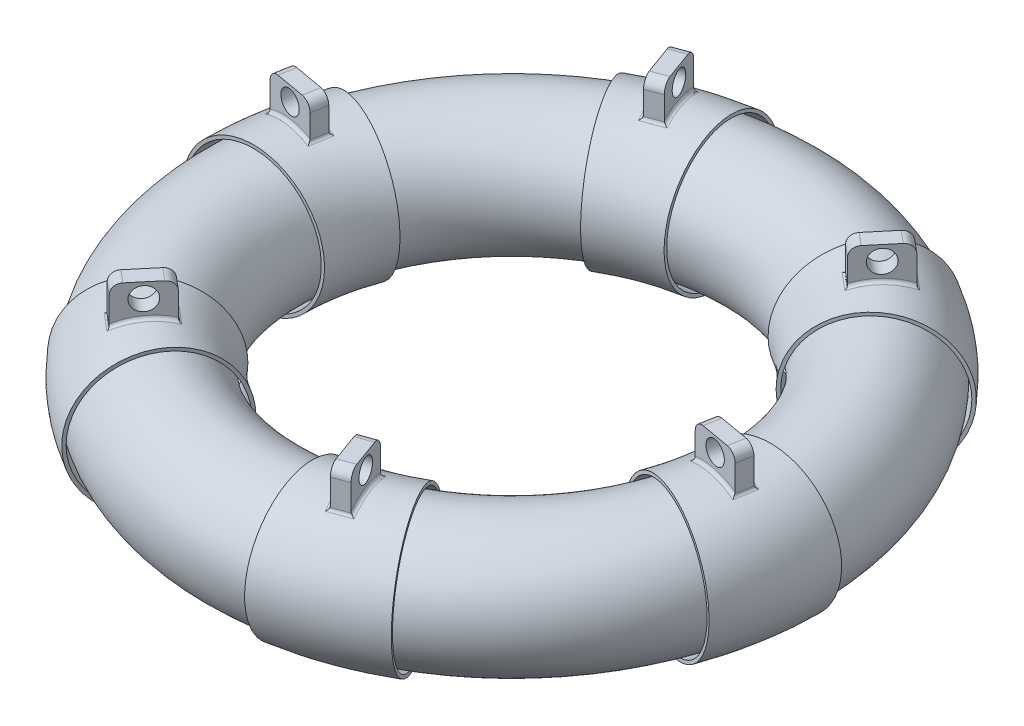
SolidWorks part; units mm, degrees
ref_plane "Front Plane" through (0, 0, 0) normal (0, 0, 1) x (1, 0, 0)
ref_plane "Top Plane" through (0, 0, 0) normal (0, 1, 0) x (1, 0, 0)
ref_plane "Right Plane" through (0, 0, 0) normal (1, 0, 0) x (0, 0, -1)
sketch "Sketch1" plane through (0, 0, 0) normal (0, 0, 1) x (1, 0, 0)
  line L0 (0, 0) -> (-100, 0) construction
  line L1 (0, 14.2155) -> (0, -15.5415) construction
  circle A0 centre (-80, 0) radius 20
  dimension "D2" = 40
  dimension "D1" = 100
revolve "Revolve1" add sketch "Sketch1" angle 360 about L1
sketch "Sketch2" plane through (0, 0, 0) normal (0, 0, 1) x (1, 0, 0)
  line L0 (0, 0) -> (0, 19.2706) construction
  line L1 (110, 0) -> (-110, 0) construction
  circle A0 centre (-80, 0) radius 21
revolve "Revolve-Thin1" add sketch "Sketch2" angle 20 about L0
sketch "Sketch3" plane through (0, 0, 0) normal (0, 1, 0) x (1, 0, 0)
  line L0 (0, 0) -> (-100.4504, 17.7121) construction
  line L1 (-100.4504, 17.7121) -> (-79.8488, 14.0795) construction
  line L3 (-86.9146, 17.864) -> (-71.9146, 15.2191)
  line L4 (-86.9146, 17.864) -> (-87.7829, 12.9399)
  line L5 (-71.9146, 15.2191) -> (-72.7829, 10.295)
  line L6 (-87.7829, 12.9399) -> (-72.7829, 10.295)
  line L7 (-86.9146, 17.864) -> (-72.7829, 10.295) construction
  line L8 (-71.9146, 15.2191) -> (-87.7829, 12.9399) construction
  arc A0 (-95.8486, 34.8861) -> (-102, 0) centre (0, 0) ccw construction
  dimension "D1" = 15
  dimension "D2" = 5
extrude "Boss-Extrude1" add sketch "Sketch3" along normal blind 10 and the other way up to surface from offset 22 other way up to face at (-54.5022, 0, -19.8372)
fillet "Fillet3" radius 1 4 edges at (-79.8415, 21.9452, -16.6168) (-80.0024, 21.9842, -11.568)
fillet "Fillet4" radius 3 2 edges at (-72.3488, 32, -12.757) (-87.3488, 32, -15.4019)
sketch "Sketch5" plane through (-0.4341, 0, 2.462) normal (-0.1736, 0, 0.9848) x (0.9848, 0, 0.1736)
  line L0 (-81.0806, 32) -> (-81.0806, 22.9709) construction
  line L1 (-85.6963, 32) -> (-76.4649, 32) construction
  circle A0 centre (-81.0806, 27.4855) radius 3.5
  spline S0 degree 3 poles (-88.6963, 21.2643) (-88.0936, 21.5125) (-87.4826, 21.7342) (-86.2514, 22.1234) (-85.6302, 22.2913) (-83.75, 22.7164) (-82.4745, 22.8952) (-80.5269, 23.0013) (-79.8749, 23.0091) (-78.5784, 22.9699) (-77.932, 22.923) (-76.6428, 22.7745) (-75.9985, 22.6726) (-74.7223, 22.4149) (-74.0905, 22.2592) (-73.4649, 22.0765) knots 0 0 0 0 0.125 0.125 0.25 0.25 0.5 0.5 0.625 0.625 0.75 0.75 0.875 0.875 1 1 1 1 construction
extrude "Cut-Extrude2" cut sketch "Sketch5" against normal blind 10
pattern_circular "CirPattern3" count 6 over 360
